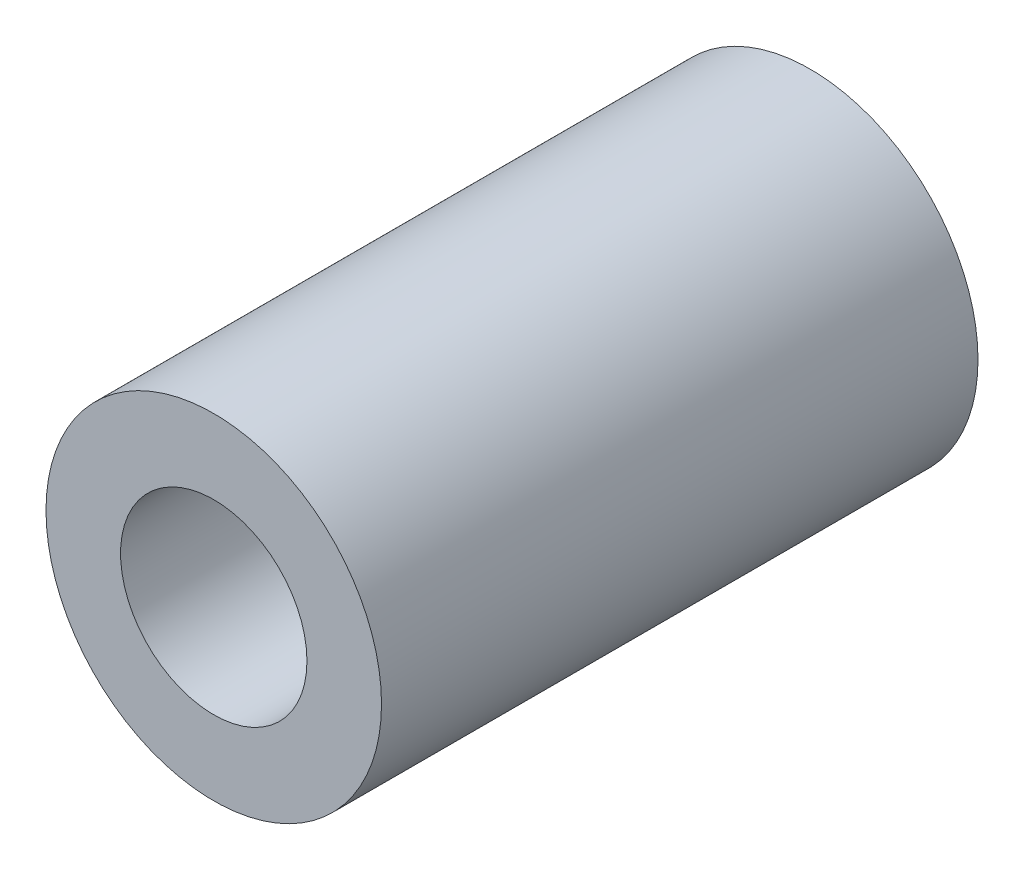
SolidWorks part; units mm, degrees
material "Cobre"
ref_plane "Plano frontal" through (0, 0, 0) normal (0, 0, 1) x (1, 0, 0)
ref_plane "Plano superior" through (0, 0, 0) normal (0, 1, 0) x (1, 0, 0)
ref_plane "Plano direito" through (0, 0, 0) normal (1, 0, 0) x (0, 0, -1)
sketch "Esboço1" plane through (0, 0, 0) normal (0, 0, 1) x (1, 0, 0)
  circle A0 centre (0, 0) radius 7.5
  circle A1 centre (0, 0) radius 13.5
  dimension "D1" = 15
  dimension "D2" = 27
extrude "Ressalto-extrusão1" add sketch "Esboço1" along normal blind 48
